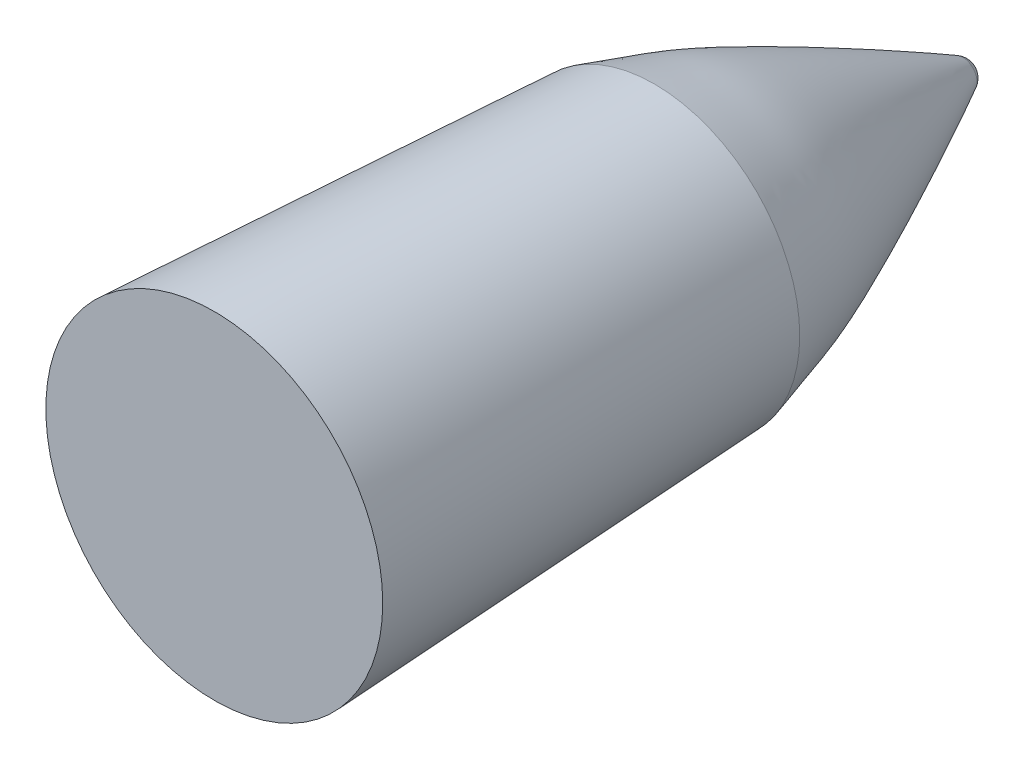
SolidWorks part; units mm, degrees
material "Свинец без примесей"
ref_plane "Спереди" through (0, 0, 0) normal (0, 0, 1) x (1, 0, 0)
ref_plane "Сверху" through (0, 0, 0) normal (0, 1, 0) x (1, 0, 0)
ref_plane "Справа" through (0, 0, 0) normal (1, 0, 0) x (0, 0, -1)
sketch "Эскиз1" plane through (0, 0, 0) normal (0, 1, 0) x (1, 0, 0)
  line L0 (0, 0) -> (0, 80) construction
  line L1 (0, 0) -> (-25, 0) construction
  line L2 (-21, 2) -> (-21, -18) construction
  line L5 (-21, -20) -> (0, -20)
  line L8 (-25, 0) -> (0, 80) construction
  line L10 (-21, 23.3035) -> (-21, -20)
  line L11 (0, 76.5095) -> (0, -20)
  line L12 (-2, -18) -> (-2, 66.8948) construction
  line L13 (-21, -18) -> (-2, -18) construction
  line L14 (0, -20) -> (0, 80) construction
  line L15 (-22.2796, 2) -> (-2, 66.8948) construction
  line L16 (-21.7437, -20) -> (0, -20) construction
  line L20 (-21, -18) -> (0, -18) construction
  line L21 (-21.7437, -20) -> (-23, -20) construction
  line L22 (-22.2796, 2) -> (-21, 2) construction
  line L23 (-23.0191, 2) -> (-21, 2) construction
  line L24 (-21, -18) -> (-21, -18) construction
  line L25 (-21, -18) -> (-21, -18) construction
  line L26 (-23, 0) -> (-23, -20) construction
  line L27 (-21, 2) -> (-21, -18) construction
  line L28 (-25, 0) -> (-23, 0) construction
  spline S0 degree 3 poles (-25, 0) (-25.3345, 19.1075) (-20.4075, 33.8926) (-15.3337, 51.5733) (-1.1082, 79.7902) (0, 80) knots 0 0 0 0 0.501806 0.601806 1 1 1 1 construction
  spline S1 degree 1 poles (-23.0191, 2) (1.1823, 78.3869) knots 0 0 1 1 construction
  spline S2 degree 3 poles (-23.0191, 2) (-23.0199, 2.538) (-23.0142, 3.6222) (-22.9746, 5.7238) (-22.8747, 8.2734) (-22.6809, 11.1999) (-22.3338, 14.9367) (-21.7512, 19.309) (-20.8698, 24.1215) (-19.8618, 28.543) (-18.781, 32.6183) (-17.6838, 36.3877) (-16.7941, 39.3248) (-16.14, 41.546) (-15.6355, 43.1976) (-15.0242, 45.0124) (-13.9372, 47.8862) (-11.955, 52.5312) (-8.9966, 58.9452) (-6.3405, 64.4155) (-4.2832, 68.5097) (-2.819, 71.3511) (-1.4799, 73.8732) (-0.5075, 75.6326) (0.1572, 76.7835) (0.5917, 77.5048) (0.8871, 77.967) (1.0813, 78.2501) (1.1449, 78.3375) (1.1823, 78.3869) knots 0.017702 0.017702 0.017702 0.017702 0.032587 0.047472 0.077243 0.107013 0.136783 0.196324 0.255865 0.315406 0.374947 0.434488 0.494029 0.523799 0.553569 0.58334 0.61311 0.672651 0.732192 0.791733 0.821503 0.851274 0.881044 0.910815 0.9257 0.940585 0.95547 0.962913 0.970355 0.970355 0.970355 0.970355 only from (-21, 23.3035) to (0, 76.5095)
  dimension "D1" = 25
  dimension "D2" = 21
  dimension "D4" = 2
  dimension "D5" = 100
revolve "Повернуть1" add sketch "Эскиз1" angle 360 about L11
sketch "Эскиз2" plane through (0, 0, 0) normal (0, 1, 0) x (1, 0, 0)
  line L0 (21, -20) -> (21, 66.972)
  line L1 (21, -20) -> (16.442, 66.972)
  line L2 (21, 66.972) -> (16.442, 66.972)
  dimension "D1" = 3
ref_axis "Ось1" through (0, 0, 20) along (0, 0, -1)
revolve "Вырез-Повернуть1" cut sketch "Эскиз2" angle 360 about axis through (0, 0, 20) along (0, 0, -1)
sketch "Эскиз3" plane through (0, 0, 0) normal (0, 1, 0) x (1, 0, 0)
  line L0 (0, 76.5095) -> (0, 74.3882)
  line L5 (1.7622, 73.3341) -> (4.0259, 73.3341)
  line L7 (4.0259, 73.3341) -> (4.0259, 76.5095)
  line L8 (4.0259, 76.5095) -> (0, 76.5095)
  arc A2 (1.7622, 73.3341) -> (0, 74.3882) centre (0, 72.3882) ccw
revolve "Вырез-Повернуть2" cut sketch "Эскиз3" angle 360 about L0
